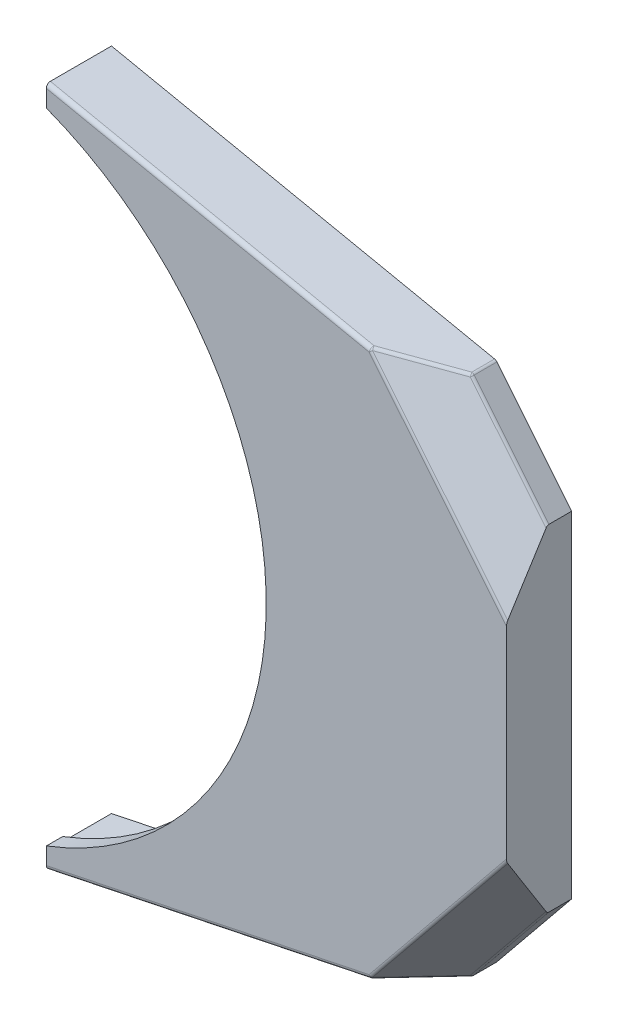
SolidWorks part; units mm, degrees
material "POM 乙缩醛共聚物"
ref_plane "前视基准面" through (0, 0, 0) normal (0, 0, 1) x (1, 0, 0)
ref_plane "上视基准面" through (0, 0, 0) normal (0, 1, 0) x (1, 0, 0)
ref_plane "右视基准面" through (0, 0, 0) normal (1, 0, 0) x (0, 0, -1)
other "Configuration Table"
sketch "草图1" plane through (0, 0, 0) normal (0, 0, 1) x (1, 0, 0)
  line L0 (15, 39.7824) -> (15, -39.7824)
  line L12 (15, 39.7824) -> (35.1156, 35.6093)
  line L13 (61.1061, 30.2174) -> (70, 19.289)
  line L14 (70, 19.289) -> (70, 3)
  line L15 (70, -19.289) -> (61.1061, -30.2174)
  line L16 (61.1061, -30.2174) -> (40.9905, -34.3905)
  line L17 (15, -39.7824) -> (15, -41.825)
  line L18 (15, -41.825) -> (62.0344, -32.0674)
  line L19 (62.3207, -31.8935) -> (71.5, -20.6144)
  line L20 (71.5, -20.6144) -> (71.5, 20.6144)
  line L21 (71.5, 20.6144) -> (62.3207, 31.8935)
  line L22 (62.0344, 32.0674) -> (15, 41.825)
  line L23 (15, 41.825) -> (15, 39.7824)
  line L24 (15, 39.7824) -> (35.1156, 35.6093)
  line L25 (61.1061, 30.2174) -> (70, 19.289)
  line L26 (70, 19.289) -> (70, 3)
  line L27 (70, -19.289) -> (61.1061, -30.2174)
  line L28 (61.1061, -30.2174) -> (40.9905, -34.3905)
  line L29 (15, -39.7824) -> (15, -41.825)
  line L30 (15, -41.825) -> (62.0344, -32.0674)
  line L31 (62.3207, -31.8935) -> (71.5, -20.6144)
  line L33 (71.5, 20.6144) -> (62.3207, 31.8935)
  line L34 (62.0344, 32.0674) -> (15, 41.825)
  line L35 (15, 41.825) -> (15, 39.7824)
  line L67 (35.1156, 35.6093) -> (34.7093, 33.651)
  line L68 (35.1156, 35.6093) -> (34.7093, 33.651)
  line L69 (40.5842, 32.4322) -> (40.9905, 34.3905)
  line L70 (40.5842, 32.4322) -> (40.9905, 34.3905)
  line L71 (40.9905, 34.3905) -> (61.1061, 30.2174)
  line L72 (40.9905, 34.3905) -> (61.1061, 30.2174)
  line L73 (70, 3) -> (68, 3)
  line L74 (70, 3) -> (68, 3)
  line L75 (68, -3) -> (70, -3)
  line L76 (68, -3) -> (70, -3)
  line L77 (70, -3) -> (70, -19.289)
  line L78 (70, -3) -> (70, -19.289)
  line L79 (40.9905, -34.3905) -> (40.5842, -32.4322)
  line L80 (40.9905, -34.3905) -> (40.5842, -32.4322)
  line L81 (34.7093, -33.651) -> (35.1156, -35.6093)
  line L82 (34.7093, -33.651) -> (35.1156, -35.6093)
  line L83 (35.1156, -35.6093) -> (15, -39.7824)
  line L84 (35.1156, -35.6093) -> (15, -39.7824)
  line L85 (71.5, -20.6144) -> (71.5, 20.6144)
  arc A6 (34.7093, 33.651) -> (40.5842, 32.4322) centre (37.6468, 33.0416) ccw
  arc A7 (34.7093, 33.651) -> (40.5842, 32.4322) centre (37.6468, 33.0416) ccw
  arc A8 (68, 3) -> (68, -3) centre (68, 0) ccw
  arc A9 (68, 3) -> (68, -3) centre (68, 0) ccw
  arc A10 (40.5842, -32.4322) -> (34.7093, -33.651) centre (37.6468, -33.0416) ccw
  arc A11 (40.5842, -32.4322) -> (34.7093, -33.651) centre (37.6468, -33.0416) ccw
  arc A16 (62.3207, 31.8935) -> (62.0344, 32.0674) centre (61.9329, 31.5778) ccw
  arc A17 (62.3207, 31.8935) -> (62.0344, 32.0674) centre (61.9329, 31.5778) ccw
  arc A18 (62.0344, -32.0674) -> (62.3207, -31.8935) centre (61.9329, -31.5778) ccw
  arc A19 (62.0344, -32.0674) -> (62.3207, -31.8935) centre (61.9329, -31.5778) ccw
  dimension "D1" = 0
extrude "凸台-拉伸1" add sketch "草图1" along normal blind 8 contours L28 L27 L26 L25 L24 L0 | L34 L35 L24 L25 L26 L27 L28 L29 L30 L31 L33 region at (40.2324, 0, 0) region at (16.0094, 40.8037, 0)
sketch "草图2" plane through (0, 0, 8) normal (0, 0, 1) x (1, 0, 0)
  circle A1 centre (0, 0) radius 42
  dimension "D1" = 84
extrude "切除-拉伸1" cut sketch "草图2" against normal through all both and the other way through all
chamfer "倒角1" distance 5 angle 45 2 edges at (66.9103, 26.2539, 8) (66.9103, -26.2539, 8) tangent propagation no
shell "抽壳1" thickness 2 removed face at (28.5, 0, 4) removed face at (15, 40.5276, 4) removed face at (47.874, 0, 0) removed face at (15, -40.5276, 4)
sketch "草图7" plane through (0, 0, 0) normal (0, 0, -1) x (-1, 0, 0)
  line L0 (-68, 0) -> (-70, 0) construction
  line L1 (-37.6468, 33.0416) -> (-38.053, 34.9999) construction
  line L2 (-70, -3) -> (-68, -3)
  line L3 (-68, 3) -> (-70, 3)
  line L4 (-70, -3) -> (-68, -3)
  line L5 (-68, 3) -> (-70, 3)
  line L6 (-40.9905, 34.3905) -> (-40.5842, 32.4322)
  line L7 (-34.7093, 33.651) -> (-35.1156, 35.6093)
  line L8 (-40.9905, 34.3905) -> (-40.5842, 32.4322)
  line L9 (-34.7093, 33.651) -> (-35.1156, 35.6093)
  line L10 (-40.5842, -32.4322) -> (-40.9905, -34.3905)
  line L11 (-35.1156, -35.6093) -> (-34.7093, -33.651)
  line L12 (-40.5842, -32.4322) -> (-40.9905, -34.3905)
  line L13 (-35.1156, -35.6093) -> (-34.7093, -33.651)
  line L14 (-37.6468, -33.0416) -> (-38.053, -34.9999) construction
  line L15 (-68, 0) -> (-70, 0)
  line L16 (-37.6468, 33.0416) -> (-38.053, 34.9999)
  line L17 (-37.6468, -33.0416) -> (-38.053, -34.9999)
  line L18 (-35.1156, -35.6093) -> (-40.9905, -34.3905)
  line L19 (-70, -3) -> (-70, 3)
  line L20 (-40.9905, 34.3905) -> (-35.1156, 35.6093)
  arc A2 (-68, -3) -> (-68, 3) centre (-68, 0) ccw
  arc A3 (-70, 3) -> (-70, -3) centre (-70, 0) ccw
  arc A4 (-68, -3) -> (-68, 3) centre (-68, 0) ccw
  arc A5 (-70, 3) -> (-70, -3) centre (-70, 0) ccw
  arc A6 (-40.5842, 32.4322) -> (-34.7093, 33.651) centre (-37.6468, 33.0416) ccw
  arc A7 (-35.1156, 35.6093) -> (-40.9905, 34.3905) centre (-38.053, 34.9999) ccw
  arc A8 (-40.5842, 32.4322) -> (-34.7093, 33.651) centre (-37.6468, 33.0416) ccw
  arc A9 (-35.1156, 35.6093) -> (-40.9905, 34.3905) centre (-38.053, 34.9999) ccw
  arc A10 (-34.7093, -33.651) -> (-40.5842, -32.4322) centre (-37.6468, -33.0416) ccw
  arc A11 (-40.9905, -34.3905) -> (-35.1156, -35.6093) centre (-38.053, -34.9999) ccw
  arc A12 (-34.7093, -33.651) -> (-40.5842, -32.4322) centre (-37.6468, -33.0416) ccw
  arc A13 (-40.9905, -34.3905) -> (-35.1156, -35.6093) centre (-38.053, -34.9999) ccw
  line M14 (-61.1061, 30.2174) -> (-15, 39.7824)
  line M22 (-15, -39.7824) -> (-61.1061, -30.2174)
  dimension "D1" = 0
  dimension "D2" = 0
  dimension "D3" = 0
extrude "凸台-拉伸3" add sketch "草图7" against normal up to next contours L8 A8 L9 M14 | L4 A4 L5 | L13 A12 L12 M22 region at (67.7704, 0, 0) region at (37.6001, 32.8169, 0) region at (37.6001, -32.8169, 0)
sketch "草图8" plane through (0, 0, 0) normal (0, 0, -1) x (-1, 0, 0)
  circle A1 centre (-37.6468, -33.0416) radius 1.525
  circle A2 centre (-37.6468, -33.0416) radius 1.525
  circle A3 centre (-68, 0) radius 1.525
  circle A4 centre (-68, 0) radius 1.525
  circle A5 centre (-37.6468, 33.0416) radius 1.525
  circle A6 centre (-37.6468, 33.0416) radius 1.525
  dimension "D1" = 0
  dimension "D2" = 0
  dimension "D3" = 0
extrude "切除-拉伸2" cut sketch "草图8" against normal blind 3.4
chamfer "倒角2" distance 0.5 angle 45 3 edges at (36.1218, 33.0416, 0) (66.475, 0, 0) (36.1218, -33.0416, 0)
fillet "圆角2" radius 0.5 10 edges at (66.9103, 26.2539, 3) (66.9103, -26.2539, 3) (62.9762, 23.1668, 8) (62.9762, -23.1668, 8) (34.7262, 37.7327, 8) (34.7262, -37.7327, 8) (58.2434, 32.8539, 5.5561) (62.1926, 32.0051, 3.0289) (58.2434, -32.8539, 5.5561) (62.1926, -32.0051, 3.0289)
